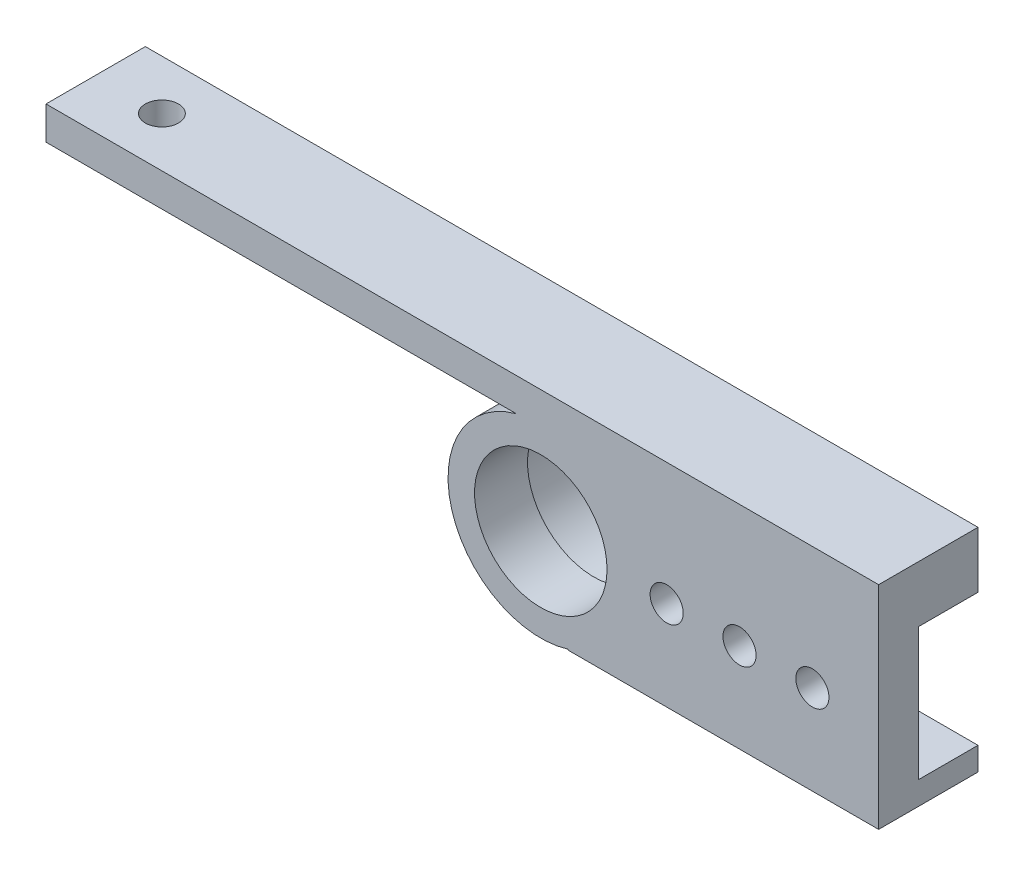
SolidWorks part; units mm, degrees
ref_plane "前视基准面" through (0, 0, 0) normal (0, 0, 1) x (1, 0, 0)
ref_plane "上视基准面" through (0, 0, 0) normal (0, 1, 0) x (1, 0, 0)
ref_plane "右视基准面" through (0, 0, 0) normal (1, 0, 0) x (0, 0, -1)
sketch "草图1" plane through (0, 0, 0) normal (0, 0, 1) x (1, 0, 0)
  line L1 (20, -10) -> (-20, -10)
  line L2 (20, -10) -> (20, 10)
  line L3 (20, 10) -> (-20, 10)
  line L4 (-20, -10) -> (-20, 10)
  line L5 (20, -10) -> (-20, 10) construction
  line L6 (20, 10) -> (-20, -10) construction
  point P0 (0, 0)
  dimension "D1" = 40
  dimension "D2" = 20
extrude "凸台-拉伸1" add sketch "草图1" along normal blind 6
sketch "草图2" plane through (0, 0, 6) normal (0, 0, 1) x (1, 0, 0)
  line L0 (20, -10) -> (20, 10) construction
  circle A0 centre (10, 0) radius 2.5
  circle A1 centre (-1, 0) radius 2.5
  circle A2 centre (-12, 0) radius 2.5
  dimension "D1" = 10
  dimension "D2" = 5
  dimension "D3" = 3
extrude "切除-拉伸1" cut sketch "草图2" against normal through all
sketch "草图3" plane through (0, 0, 6) normal (0, 0, 1) x (1, 0, 0)
  line L0 (20, 13.5) -> (20, 10)
  line L1 (20, -13.5) -> (-26.894, -13.5)
  line L3 (20, 13.5) -> (-26.894, 13.5)
  line L4 (-20, 10) -> (-20, -10)
  line L5 (-20, -10) -> (20, -10)
  line L6 (20, -10) -> (20, 10)
  line L7 (20, 10) -> (-20, 10)
  line L8 (-20, 10) -> (-20, -10)
  line L9 (-20, -10) -> (20, -10)
  line L10 (20, -10) -> (20, 10)
  line L11 (20, 10) -> (-20, 10)
  line L12 (-26.894, -13.5) -> (-26.894, 13.5)
  line L13 (20, -10.0394) -> (-26.894, 13.5) construction
  line L14 (20, 10.0394) -> (-26.894, -13.5) construction
  line L15 (20, -10) -> (20, -13.5)
  circle A0 centre (-31, 0) radius 11
  circle A1 centre (-31, 0) radius 14
  point P2 (0, 0)
  line M10 (-20, 10) -> (-20, -10)
  line M11 (-20, -10) -> (20, -10)
  line M13 (20, 10) -> (-20, 10)
  dimension "D3" = 22
  dimension "D4" = 28
  dimension "D2" = 3.5
  dimension "D1" = 0
extrude "凸台-拉伸2" add sketch "草图3" against normal blind 15 contours L3 A1 L1 L12 A0 | A1 L1 L15 M11 M10 | L1 A1 L8 A0 L12 | L8 A1 L3 L12 A0 | L8 A1 | A1 L0 L3 M10 M13 region at (-1.9449, 11.7771, 6) region at (-1.9449, -11.7771, 6) region at (-23.0173, 9.0328, 6) region at (-27.2274, 11.7946, 6) region at (-18.7882, 0, 6) region at (-23.0173, -9.0328, 6)
sketch "草图5" plane through (0, 0, 6) normal (0, 0, 1) x (1, 0, 0)
  circle A0 centre (-31, 0) radius 10
  circle A1 centre (-31, 0) radius 11 construction
  circle A2 centre (-31, 0) radius 11
  dimension "D1" = 20
extrude "凸台-拉伸3" add sketch "草图5" against normal blind 8
sketch "草图6" plane through (0, 0, 6) normal (0, 0, 1) x (1, 0, 0)
  circle A0 centre (-31, 0) radius 8.5
  circle A1 centre (-31, 0) radius 10 construction
  circle A2 centre (-31, 0) radius 10
  dimension "D1" = 17
sketch "草图7" plane through (0, 13.5, 0) normal (0, 1, 0) x (1, 0, 0)
  circle A0 centre (-16.8213, 3.0525) radius 3.3366
sketch "草图8" plane through (20, 0, 0) normal (1, 0, 0) x (0, 0, -1)
  line L1 (-6, 13.5) -> (9, 13.5)
  line L2 (-6, 13.5) -> (-6, 18.5)
  line L3 (-6, 18.5) -> (9, 18.5)
  line L4 (9, 13.5) -> (9, 18.5)
  dimension "D1" = 5
extrude "凸台-拉伸4" add sketch "草图8" against normal blind 200
sketch "草图9" plane through (0, 0, 6) normal (0, 0, 1) x (1, 0, 0)
  line L1 (-29.5663, 15.6648) -> (-25.1627, 15.6648)
  line L2 (-29.5663, 15.6648) -> (-29.5663, 11.9284)
  line L3 (-29.5663, 11.9284) -> (-25.1627, 11.9284)
  line L4 (-25.1627, 15.6648) -> (-25.1627, 11.9284)
extrude "凸台-拉伸5" add sketch "草图9" against normal through all
sketch "草图11" plane through (0, 18.5, 0) normal (0, 1, 0) x (1, 0, 0)
  line L0 (-105.6913, -6) -> (-105.6913, 9)
  line L1 (-180, -6) -> (20, -6) construction
  line L2 (-105.6913, 350.4998) -> (-105.6913, -19.5002) construction
  line L3 (-180, 9) -> (20, 9) construction
sketch "草图13" plane through (0, 18.5, 0) normal (0, 1, 0) x (1, 0, 0)
  line L1 (-105.6913, -6) -> (-183.1111, -6)
  line L2 (-105.6913, -6) -> (-105.6913, 12.5245)
  line L3 (-105.6913, 12.5245) -> (-183.1111, 12.5245)
  line L4 (-183.1111, -6) -> (-183.1111, 12.5245)
extrude "切除-拉伸2" cut sketch "草图13" against normal through all
sketch "草图14" plane through (0, 18.5, 0) normal (0, 1, 0) x (1, 0, 0)
  line L0 (-105.6913, 1.5) -> (-95.6913, 1.5) construction
  line L1 (-105.6913, -6) -> (-105.6913, 9) construction
  circle A0 centre (-95.6913, 1.5) radius 2.5
  dimension "D2" = 5
  dimension "D1" = 10
extrude "切除-拉伸3" cut sketch "草图14" against normal blind 10
